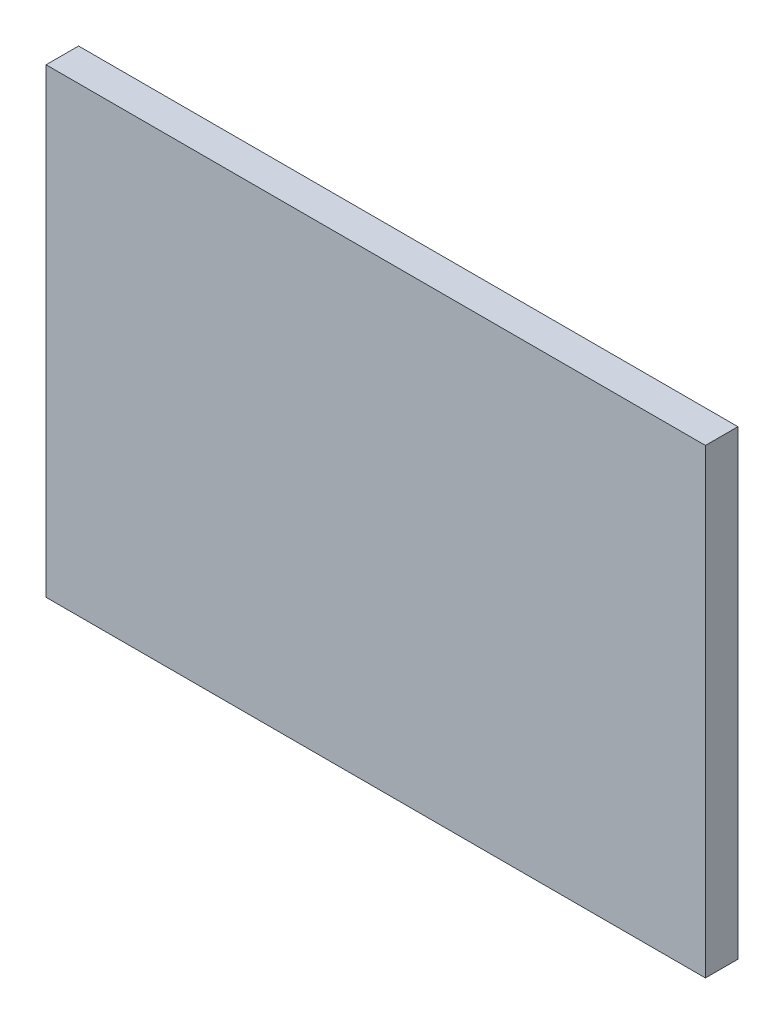
SolidWorks part; units mm, degrees
ref_plane "Front Plane" through (0, 0, 0) normal (0, 0, 1) x (1, 0, 0)
ref_plane "Top Plane" through (0, 0, 0) normal (0, 1, 0) x (1, 0, 0)
ref_plane "Right Plane" through (0, 0, 0) normal (1, 0, 0) x (0, 0, -1)
sketch "Sketch1" plane through (0, 0, 0) normal (0, 0, 1) x (1, 0, 0)
  line L1 (101.5, -71) -> (-101.5, -71)
  line L2 (101.5, -71) -> (101.5, 71)
  line L3 (101.5, 71) -> (-101.5, 71)
  line L4 (-101.5, -71) -> (-101.5, 71)
  line L5 (101.5, -71) -> (-101.5, 71) construction
  line L6 (101.5, 71) -> (-101.5, -71) construction
  point P0 (0, 0)
  dimension "D1" = 203
  dimension "D2" = 142
extrude "Boss-Extrude1" add sketch "Sketch1" along normal mid plane 10
